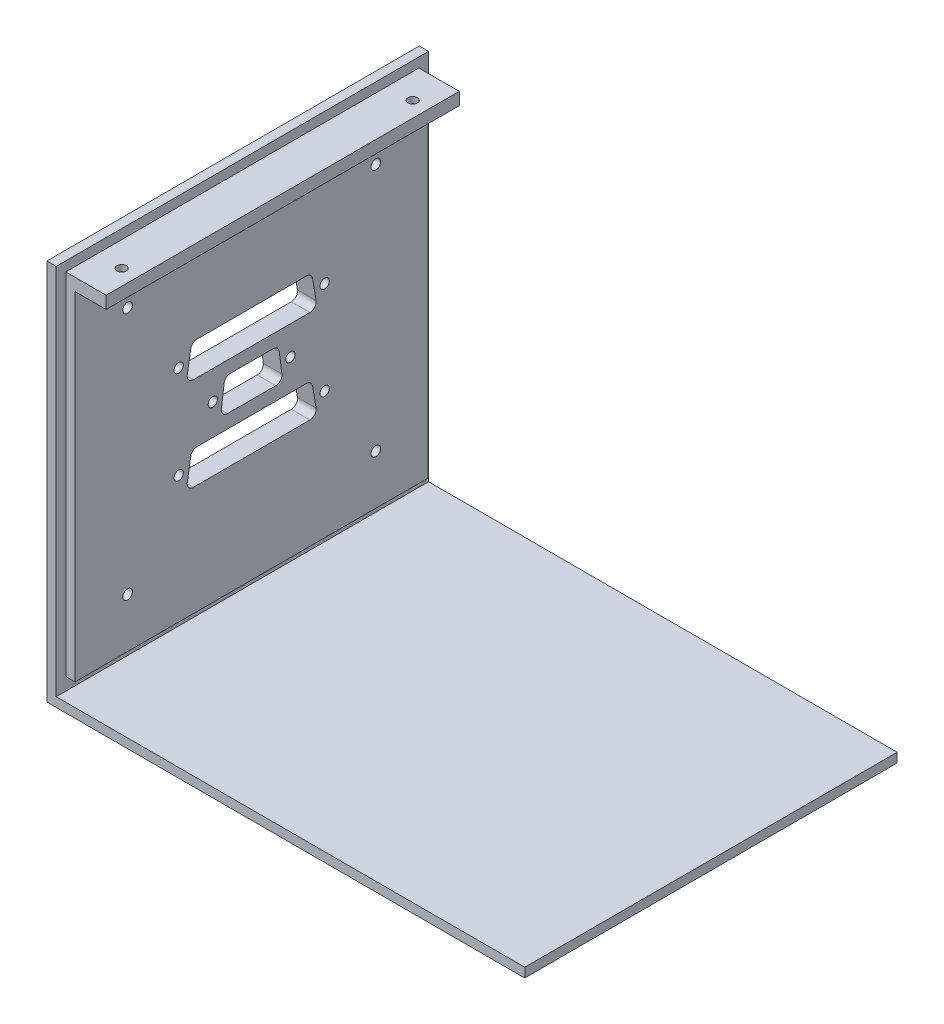
SolidWorks part; units mm, degrees
other "Markup1"
sketch "Sketch5" plane through (-105, 0, 60.5) normal (-0.0451, -0.9984, 0.0353) x (-0.7444, 0.01, -0.6676)
other "Markup2"
sketch "Sketch6" plane through (97, 11, -60) normal (0.0014, 0.7787, -0.6274) x (0.9996, 0.0165, 0.0227)
ref_plane "Front Plane" through (0, 0, 0) normal (0, 0, 1) x (1, 0, 0)
ref_plane "Top Plane" through (0, 0, 0) normal (0, 1, 0) x (1, 0, 0)
ref_plane "Right Plane" through (0, 0, 0) normal (1, 0, 0) x (0, 0, -1)
sketch "Sketch1" plane through (0, 0, 0) normal (0, 1, 0) x (1, 0, 0)
  line L1 (-77, 60) -> (77, 60)
  line L2 (-77, 60) -> (-77, -60)
  line L3 (-77, -60) -> (77, -60)
  line L4 (77, 60) -> (77, -60)
  point P4 (0, 60)
  point P5 (-77, 0)
  dimension "D1" = 120
  dimension "D2" = 154
extrude "Large-Wall-Outer" add sketch "Sketch1" along normal blind 3
sketch "Sketch8" plane through (0, 3, 0) normal (0, 1, 0) x (1, 0, 0)
  line L0 (-77, -60) -> (77, -60) construction
  line L1 (-77, 60) -> (-74, 60)
  line L2 (-77, 60) -> (-77, -60)
  line L3 (-77, -60) -> (-74, -60)
  line L4 (-74, 60) -> (-74, -60)
  dimension "D1" = 3
extrude "Small-Wall-Outer" add sketch "Sketch8" along normal blind 120.1
sketch "Sketch10" plane through (-74, 0, 0) normal (1, 0, 0) x (0, 0, -1)
  line L1 (-56.9, 7.1) -> (56.9, 7.1)
  line L2 (-56.9, 7.1) -> (-56.9, 120)
  line L3 (-56.9, 120) -> (56.9, 120)
  line L4 (56.9, 7.1) -> (56.9, 120)
  point P4 (0, 120)
  dimension "D1" = 112.9
  dimension "D2" = 113.8
  dimension "D3" = 3.1
extrude "Small-Wall-Inner" add sketch "Sketch10" along normal blind 3
sketch "Sketch14" plane through (-71, 0, 0) normal (1, 0, 0) x (0, 0, -1)
  line L1 (56.9, 116) -> (-56.9, 116)
  line L2 (56.9, 116) -> (56.9, 120)
  line L3 (56.9, 120) -> (-56.9, 120)
  line L4 (-56.9, 116) -> (-56.9, 120)
  point P4 (0, 0)
  point P6 (0, 0)
  dimension "D1" = 4
extrude "Mount" add sketch "Sketch14" along normal blind 10
sketch "Sketch17" plane through (0, 116, 0) normal (0, -1, 0) x (1, 0, 0)
  line L0 (-61, 56.9) -> (-71, 56.9) construction
  line L1 (-66, 43.7) -> (-63.2287, 45.3)
  line L2 (-63.2287, 45.3) -> (-63.2287, 48.5)
  line L3 (-63.2287, 48.5) -> (-66, 50.1)
  line L4 (-66, 50.1) -> (-68.7713, 48.5)
  line L5 (-68.7713, 48.5) -> (-68.7713, 45.3)
  line L6 (-68.7713, 45.3) -> (-66, 43.7)
  line L7 (-61, -56.9) -> (-71, -56.9) construction
  line L8 (-66, -50.1) -> (-63.2287, -48.5)
  line L9 (-63.2287, -48.5) -> (-63.2287, -45.3)
  line L10 (-63.2287, -45.3) -> (-66, -43.7)
  line L11 (-66, -43.7) -> (-68.7713, -45.3)
  line L12 (-68.7713, -45.3) -> (-68.7713, -48.5)
  line L13 (-68.7713, -48.5) -> (-66, -50.1)
  circle A0 centre (-66, 46.9) radius 3.2 construction
  circle A1 centre (-66, -46.9) radius 3.2 construction
  point P12 (-66, -56.9)
  point P13 (0, 0)
  point P16 (-66, 56.9)
  point P17 (0, 0)
  point P19 (0, 0)
  point P27 (0, 0)
  dimension "D1" = 10
  dimension "D3" = 6.4
  dimension "D4" = 6.4
  dimension "D2" = 10
extrude "Mounting-Nuts" cut sketch "Sketch17" against normal blind 2
sketch "Sketch18" plane through (0, 118, 0) normal (0, -1, 0) x (1, 0, 0)
  line L0 (-68.7713, 48.5) -> (-68.7713, 45.3) construction
  circle A0 centre (-66, 46.9) radius 1.5
  point P2 (0, 0)
  point P3 (0, 0)
  point P8 (-68.7713, 46.9)
  dimension "D1" = 3
extrude "Nut-1-Bolt-Hole" cut sketch "Sketch18" against normal up to next
sketch "Sketch19" plane through (0, 118, 0) normal (0, -1, 0) x (1, 0, 0)
  line L0 (-68.7713, -45.3) -> (-68.7713, -48.5) construction
  circle A0 centre (-66, -46.9) radius 1.5
  point P2 (0, 0)
  point P6 (-68.7713, -46.9)
  dimension "D1" = 3
extrude "Nut-2-Bolt-Hole" cut sketch "Sketch19" against normal up to next
sketch "Sketch23" plane through (-77, 0, 0) normal (-1, 0, 0) x (0, 0, -1)
  line L0 (-12.5, -63.05) -> (12.5, -63.05) construction
  line L1 (-23.52, -78.05) -> (23.52, -78.05) construction
  line L2 (-6.8916, -68.1679) -> (6.8916, -68.1679)
  line L4 (-7.7666, -57.4179) -> (7.7666, -57.4179)
  line L6 (-17.6522, -83.0962) -> (17.6522, -83.0962)
  line L8 (-18.7772, -72.3462) -> (18.7772, -72.3462)
  line L10 (-23.52, -48.05) -> (23.52, -48.05) construction
  line L11 (-17.6522, -53.0962) -> (17.6522, -53.0962)
  line L13 (-18.7772, -42.3462) -> (18.7772, -42.3462)
  line L16 (-19.625, -51.425) -> (-20.75, -44.675)
  line L19 (20.75, -44.675) -> (19.625, -51.425)
  line L22 (-8.875, -66.425) -> (-9.75, -59.675)
  line L25 (9.75, -59.675) -> (8.875, -66.425)
  line L28 (-20.75, -74.675) -> (-19.625, -81.425)
  line L31 (19.625, -81.425) -> (20.75, -74.675)
  line L32 (60, -123.1) -> (-60, -123.1) construction
  line L34 (60, -123.1) -> (60, -3) construction
  circle A0 centre (-12.5, -63.05) radius 1.5
  circle A1 centre (12.5, -63.05) radius 1.5
  circle A2 centre (-23.52, -78.05) radius 1.5
  circle A3 centre (23.52, -78.05) radius 1.5
  circle A4 centre (-23.52, -48.05) radius 1.5
  circle A5 centre (23.52, -48.05) radius 1.5
  arc A6 (18.7772, -42.3462) -> (20.75, -44.675) centre (18.7772, -44.3462) cw
  arc A7 (-18.7772, -42.3462) -> (-20.75, -44.675) centre (-18.7772, -44.3462) ccw
  arc A8 (17.6522, -53.0962) -> (19.625, -51.425) centre (17.6522, -51.0962) ccw
  arc A9 (-17.6522, -53.0962) -> (-19.625, -51.425) centre (-17.6522, -51.0962) cw
  arc A10 (20.75, -74.675) -> (18.7772, -72.3462) centre (18.7772, -74.3462) ccw
  arc A11 (17.6522, -83.0962) -> (19.625, -81.425) centre (17.6522, -81.0962) ccw
  arc A12 (-19.625, -81.425) -> (-17.6522, -83.0962) centre (-17.6522, -81.0962) ccw
  arc A13 (-20.75, -74.675) -> (-18.7772, -72.3462) centre (-18.7772, -74.3462) cw
  arc A14 (7.7666, -57.4179) -> (9.75, -59.675) centre (7.7666, -59.4179) cw
  arc A15 (8.875, -66.425) -> (6.8916, -68.1679) centre (6.8916, -66.1679) cw
  arc A16 (-8.875, -66.425) -> (-6.8916, -68.1679) centre (-6.8916, -66.1679) ccw
  arc A17 (-9.75, -59.675) -> (-7.7666, -57.4179) centre (-7.7666, -59.4179) cw
  point P4 (0, -63.05)
  point P8 (0, -123.1)
  point P9 (0, -57.4179)
  point P11 (0, 0)
  point P12 (0, 0)
  point P17 (0, -78.05)
  point P19 (60, -63.05)
  point P23 (-9.3125, -63.05)
  point P24 (0, -83.0962)
  point P29 (0, -63.05)
  point P38 (20.1875, -78.05)
  point P39 (-20.1875, -48.05)
  point P41 (9.3125, -63.05)
  point P42 (20.1875, -48.05)
  point P45 (-20.1875, -78.05)
  point P52 (21.1381, -42.3462)
  point P59 (19.3465, -53.0962)
  point P66 (21.1381, -72.3462)
  point P69 (19.3465, -83.0962)
  point P76 (10.0426, -57.4179)
  point P79 (8.6491, -68.1679)
  dimension "D1" = 3
  dimension "D2" = 3
  dimension "D8" = 3
  dimension "D7" = 3
  dimension "D14" = 3
  dimension "D15" = 3
  dimension "D4" = 41.5
  dimension "D5" = 11.02
  dimension "D21" = 2
  dimension "D25" = 2
  dimension "D27" = 2
  dimension "D3" = 25
  dimension "D6" = 10.75
  dimension "D9" = 47.04
  dimension "D13" = 15
  dimension "D18" = 10.75
  dimension "D19" = 15
  dimension "D20" = 10.75
  dimension "D28" = 39.25
  dimension "D30" = 41.5
  dimension "D31" = 39.25
  dimension "D32" = 19.5
  dimension "D33" = 17.75
extrude "Connector-Slots" cut sketch "Sketch23" against normal up to next
sketch "Sketch27" plane through (-77, 0, 0) normal (-1, 0, 0) x (0, 0, 1)
  line L0 (-60, 0) -> (60, 0) construction
  circle A0 centre (-40, 23.05) radius 1.55
  circle A2 centre (12.5, 63.05) radius 1.5 construction
  circle A3 centre (-12.5, 63.05) radius 1.5 construction
  circle A4 centre (12.5, 63.05) radius 1.5
  circle A5 centre (-12.5, 63.05) radius 1.5
  circle A6 centre (40, 23.05) radius 1.55
  circle A7 centre (40, 103.05) radius 1.55
  circle A8 centre (-40, 103.05) radius 1.55
  point P12 (0, 63.05)
  point P15 (0, 0)
  dimension "D1" = 3.1
  dimension "D2" = 40
  dimension "D3" = 40
  dimension "D4" = 2
  dimension "D5" = 2
extrude "PCB-Mount-Holes" cut sketch "Sketch27" against normal up to next (6 mm away)
